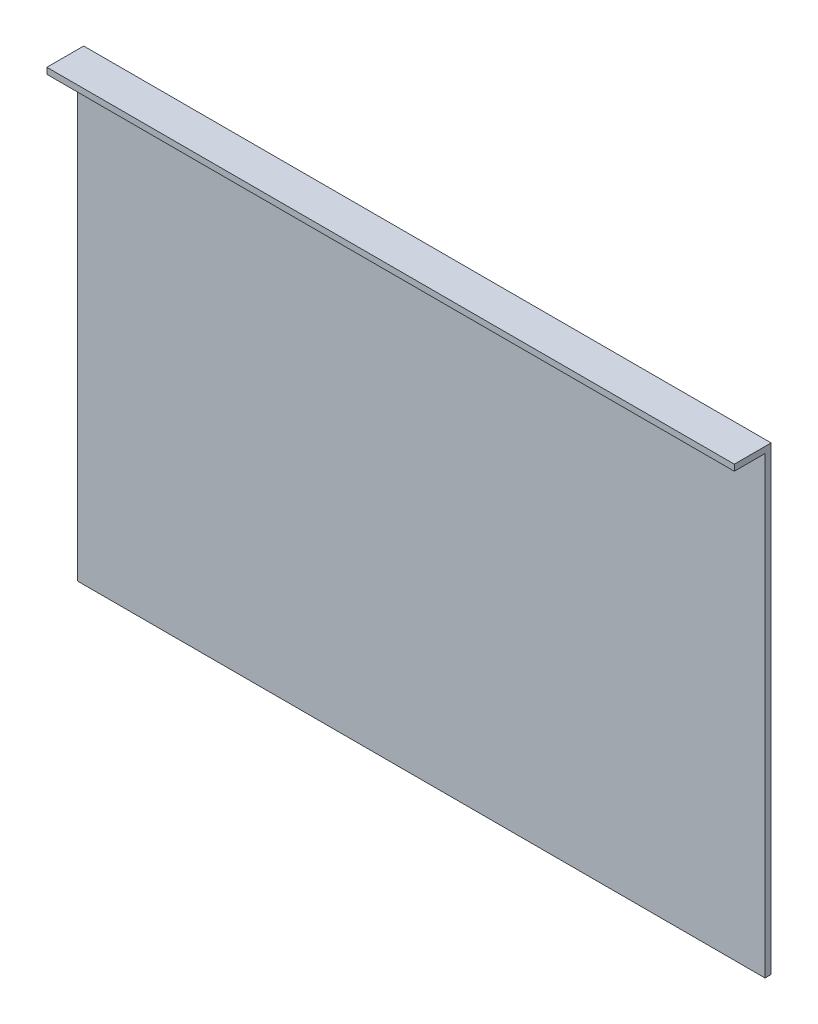
SolidWorks part; units mm, degrees
material "6061-T6 (SS)"
ref_plane "Front" through (0, 0, 0) normal (0, 0, 1) x (1, 0, 0)
ref_plane "Top" through (0, 0, 0) normal (0, 1, 0) x (1, 0, 0)
ref_plane "Right" through (0, 0, 0) normal (1, 0, 0) x (0, 0, -1)
sketch "Sketch1" plane through (0, 0, 0) normal (0, 0, 1) x (1, 0, 0)
  line L1 (0, 0) -> (448, 0)
  line L2 (0, 0) -> (0, 300)
  line L3 (0, 300) -> (448, 300)
  line L4 (448, 0) -> (448, 300)
  dimension "D1" = 300
  dimension "D2" = 448
base flange "Base-Flange1" sketch "Sketch1" thickness 4 reverse thickness direction no parameters "D1"=1
sketch "Sketch13" plane through (0, 0, 0) normal (0, 0, 1) x (1, 0, 0)
  line L0 (448, 0) -> (448, 300) construction
  line L1 (0, 300) -> (448, 300)
  line L2 (0, 300) -> (0, 296)
  line L3 (0, 296) -> (448, 296)
  line L4 (448, 300) -> (448, 296)
  dimension "D1" = 4
extrude "Boss-Extrude1" add sketch "Sketch13" along normal blind 20
sketch "Bend-Lines1" [suppressed] plane through (0, 0, 0) normal (0, 1, 0) x (1, 0, 0)
sketch "Bounding-Box1" [suppressed] plane through (0, 0, 0) normal (0, 1, 0) x (1, 0, 0)
sheet metal parameters "Sheet-Metal1" thickness 4 parameters "D1"=1
flat pattern "Flat-Pattern1" [suppressed]
sketch "Bend-Lines2" plane through (0, 0, 0) normal (0, 1, 0) x (1, 0, 0)
sketch3d "Bounding-Box2" [suppressed]
  line L0 (0, 0, 0) -> (448, 0, 0) construction
  line L1 (0, 300, 0) -> (448, 300, 0) construction
  line L2 (0, 0, 0) -> (0, 300, 0) construction
  line L3 (448, 0, 0) -> (448, 300, 0) construction
sheet metal parameters "Sheet-Metal4" thickness 4 parameters "D1"=1
flat pattern "Flat-Pattern1"
sketch "Bend-Lines2" plane through (0, 0, 0) normal (0, 1, 0) x (1, 0, 0)
sketch3d "Bounding-Box2" [suppressed]
  line L0 (0, 0, 0) -> (448, 0, 0) construction
  line L1 (0, 296, 0) -> (448, 296, 0) construction
  line L2 (0, 0, 0) -> (0, 296, 0) construction
  line L3 (448, 0, 0) -> (448, 296, 0) construction
